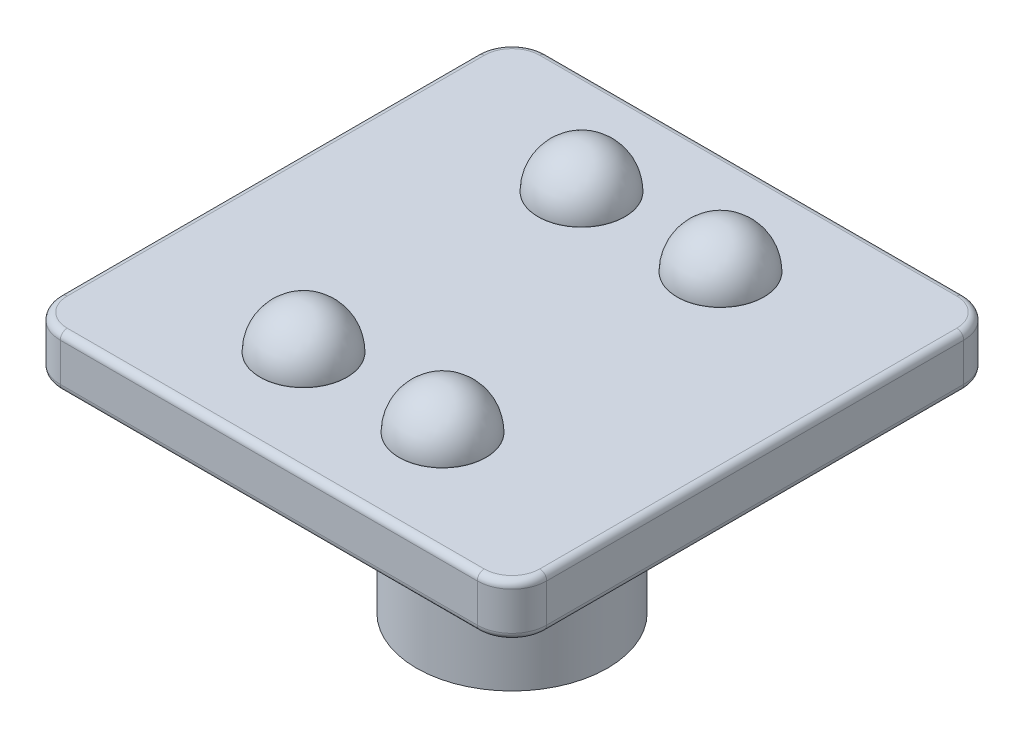
SolidWorks part; units mm, degrees
ref_plane "Front Plane" through (0, 0, 0) normal (0, 0, 1) x (1, 0, 0)
ref_plane "Top Plane" through (0, 0, 0) normal (0, 1, 0) x (1, 0, 0)
ref_plane "Right Plane" through (0, 0, 0) normal (1, 0, 0) x (0, 0, -1)
sketch "Sketch1" plane through (0, 0, 0) normal (0, 1, 0) x (1, 0, 0)
  line L1 (-7.3247, 4.3967) -> (4.6753, 4.3967)
  line L2 (-8.3247, 3.3967) -> (-8.3247, -8.6033)
  line L3 (-7.3247, -9.6033) -> (4.6753, -9.6033)
  line L4 (5.6753, 3.3967) -> (5.6753, -8.6033)
  arc A0 (-8.3247, -8.6033) -> (-7.3247, -9.6033) centre (-7.3247, -8.6033) ccw
  arc A1 (4.6753, -9.6033) -> (5.6753, -8.6033) centre (4.6753, -8.6033) ccw
  arc A2 (4.6753, 4.3967) -> (5.6753, 3.3967) centre (4.6753, 3.3967) cw
  arc A3 (-7.3247, 4.3967) -> (-8.3247, 3.3967) centre (-7.3247, 3.3967) ccw
  point P8 (5.6753, -9.6033)
  point P11 (5.6753, 4.3967)
  point P14 (-8.3247, 4.3967)
  dimension "D3" = 1
  dimension "D1" = 14
  dimension "D2" = 14
extrude "Boss-Extrude1" add sketch "Sketch1" along normal blind 1.5
sketch "Sketch2" plane through (0, 0, 0) normal (0, -1, 0) x (1, 0, 0)
  line L0 (-7.3247, 9.6033) -> (4.6753, 9.6033) construction
  line L1 (5.6753, 8.6033) -> (5.6753, -3.3967) construction
  line L2 (-1.3247, -4.3967) -> (-1.3247, 9.6033) construction
  line L3 (-8.3247, 2.6033) -> (5.6753, 2.6033) construction
  line L4 (-8.3247, -3.3967) -> (-8.3247, 8.6033) construction
  circle A0 centre (-1.3247, 2.6033) radius 2.75
  dimension "D1" = 7
  dimension "D2" = 7
extrude "Boss-Extrude2" add sketch "Sketch2" along normal blind 6
sketch "Sketch3" plane through (0, -6, 0) normal (0, -1, 0) x (1, 0, 0)
  line L0 (-1.3247, 5.3533) -> (-1.3247, -0.1467) construction
  line L1 (-3.3247, 3.1533) -> (0.6753, 3.1533)
  line L2 (-3.3247, 3.1533) -> (-3.3247, 2.0533)
  line L3 (-3.3247, 2.0533) -> (0.6753, 2.0533)
  line L4 (0.6753, 3.1533) -> (0.6753, 2.0533)
  line L5 (-1.8747, 4.6033) -> (-0.7747, 4.6033)
  line L6 (-1.8747, 4.6033) -> (-1.8747, 0.6033)
  line L7 (-1.8747, 0.6033) -> (-0.7747, 0.6033)
  line L8 (-0.7747, 4.6033) -> (-0.7747, 0.6033)
  line L9 (-4.0747, 2.6033) -> (1.4253, 2.6033) construction
  circle A3 centre (-1.3247, 2.6033) radius 2.75 construction
  circle A4 centre (-1.3247, 2.6033) radius 2.75 construction
  dimension "D7" = 0.55
  dimension "D1" = 4
  dimension "D2" = 1.1
  dimension "D3" = 1.1
  dimension "D4" = 4
  dimension "D8" = 0.55
extrude "Cut-Extrude1" cut sketch "Sketch3" against normal blind 6 contours L8 L5 L6 L1 | L1 L8 L3 L4 | L8 L1 L6 L3 | L6 L1 L2 L3 | L8 L3 L6 L7 region at (-2.5997, -6, 2.6033) region at (-1.3247, -6, 3.8783) region at (-1.3247, -6, 2.6033) region at (-0.0497, -6, 2.6033) region at (-1.3247, -6, 1.3283)
chamfer "Chamfer1" distance 0.3 angle 45 12 edges at (-1.3247, -6, 0.6033) (-1.8747, -6, 1.3283) (-2.5997, -6, 2.0533) (-3.3247, -6, 2.6033) (-2.5997, -6, 3.1533) (-0.7747, -6, 1.3283) (-0.0497, -6, 2.0533) (0.6753, -6, 2.6033) (-0.0497, -6, 3.1533) (-0.7747, -6, 3.8783) (-1.3247, -6, 4.6033) (-1.8747, -6, 3.8783)
fillet "Fillet1" radius 1 1 edges at (-1.3247, 0, -0.1467)
sketch "Sketch4" plane through (0, 1.5, 0) normal (0, 1, 0) x (1, 0, 0)
  line L0 (-1.3247, 4.3967) -> (-1.3247, -9.6033) construction
  line L1 (4.6753, 4.3967) -> (-7.3247, 4.3967) construction
  line L2 (-7.3247, -9.6033) -> (4.6753, -9.6033) construction
  line L3 (5.6753, -2.6033) -> (-8.3247, -2.6033) construction
  line L4 (-8.3247, 3.3967) -> (-8.3247, -8.6033) construction
  line L5 (5.6753, -8.6033) -> (5.6753, 3.3967) construction
  line L6 (-3.3247, 4.3967) -> (-3.3247, -9.6033) construction
  line L7 (0.6753, 4.3967) -> (0.6753, -9.6033) construction
  line L8 (-8.3247, 1.3967) -> (5.6753, 1.3967) construction
  line L9 (5.6753, -6.6033) -> (-8.3247, -6.6033) construction
  circle A0 centre (-3.3247, 1.3967) radius 1.25
  circle A3 centre (-3.3247, -6.6033) radius 1.25
  circle A4 centre (0.6753, -6.6033) radius 1.25
  circle A5 centre (0.6753, 1.3967) radius 1.25
  dimension "D1" = 4
  dimension "D2" = 4
  dimension "D3" = 2
  dimension "D4" = 2
extrude "Boss-Extrude3" add sketch "Sketch4" along normal blind 0.01
dome "Dome1" faces to dome 1 distance 1.25 reverse direction no elliptical dome no face at (-3.3247, 1.51, -0.1467) parameters "D1"=1.25
dome "Dome2" faces to dome 1 distance 1.25 reverse direction no elliptical dome no face at (0.6753, 1.51, -0.1467) parameters "D1"=1.25
dome "Dome5" faces to dome 1 distance 1.25 reverse direction no elliptical dome no face at (-3.3247, 1.51, 7.8533) parameters "D1"=1.25
dome "Dome6" faces to dome 1 distance 1.25 reverse direction no elliptical dome no face at (0.6753, 1.51, 7.8533) parameters "D1"=1.25
fillet "Fillet3" radius 0.2 16 edges at (5.3824, 1.5, -4.1038) (5.6753, 1.5, 2.6033) (5.3824, 1.5, 9.3104) (-1.3247, 1.5, 9.6033) (-8.0318, 1.5, 9.3104) (-8.0318, 1.5, -4.1038) (-8.3247, 1.5, 2.6033) (-1.3247, 1.5, -4.3967) (5.3824, 0, 9.3104) (5.6753, 0, 2.6033) (5.3824, 0, -4.1038) (-1.3247, 0, -4.3967) (-8.0318, 0, -4.1038) (-8.3247, 0, 2.6033) (-8.0318, 0, 9.3104) (-1.3247, 0, 9.6033)
